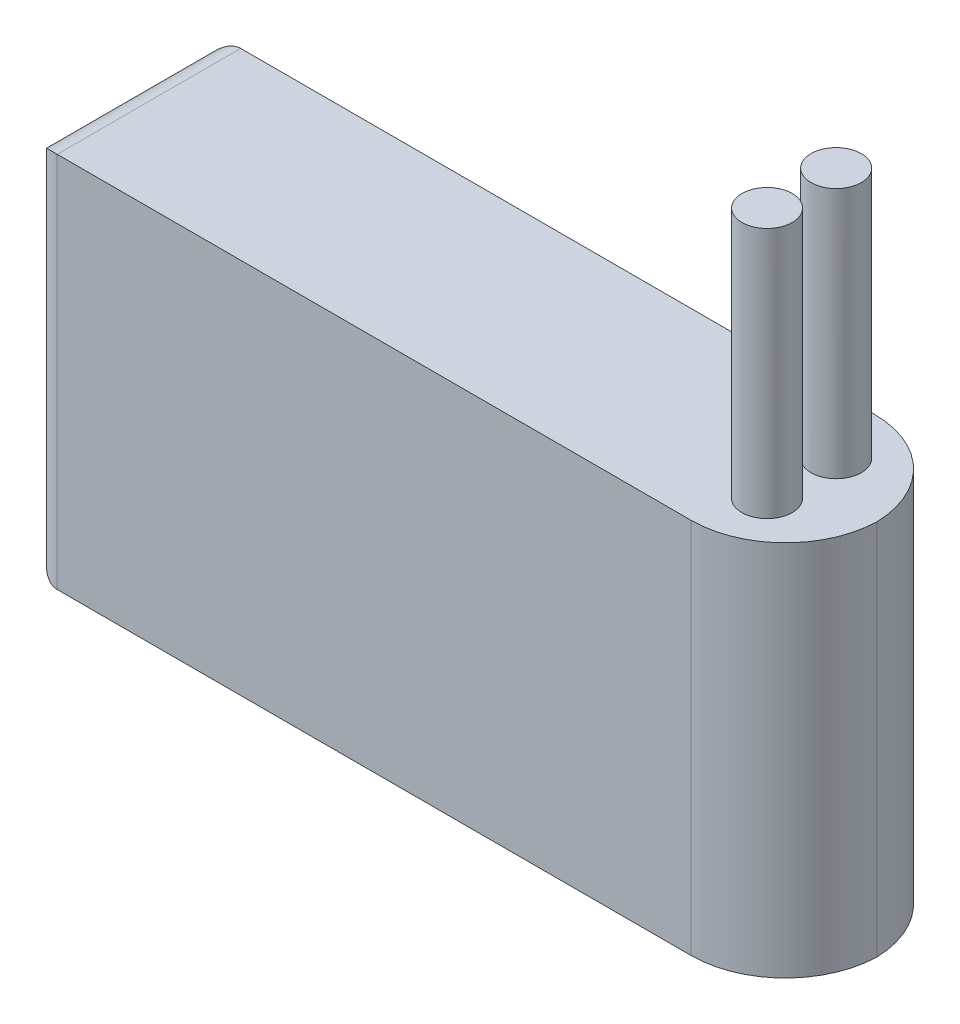
SolidWorks part; units mm, degrees
ref_plane "Front Plane" through (0, 0, 0) normal (0, 0, 1) x (1, 0, 0)
ref_plane "Top Plane" through (0, 0, 0) normal (0, 1, 0) x (1, 0, 0)
ref_plane "Right Plane" through (0, 0, 0) normal (1, 0, 0) x (0, 0, -1)
sketch "Sketch1" plane through (0, 0, 0) normal (0, 0, 1) x (1, 0, 0)
  line L1 (0, 0) -> (76.2, 0)
  line L2 (0, 0) -> (0, 38.1)
  line L3 (0, 38.1) -> (76.2, 38.1)
  line L4 (76.2, 0) -> (76.2, 38.1)
  dimension "D1" = 76.2
  dimension "D2" = 38.1
extrude "Boss-Extrude1" add sketch "Sketch1" along normal blind 18.542
fillet "Fillet1" radius 9.525 2 edges at (76.2, 19.05, 18.542) (76.2, 19.05, 0)
sketch "Sketch2" plane through (0, 38.1, 0) normal (0, 1, 0) x (1, 0, 0)
  line L0 (68.5766, -5.7785) -> (68.5766, -12.7635) construction
  line L1 (68.5766, -9.271) -> (76.1966, -9.271) construction
  circle A0 centre (68.5766, -5.7785) radius 2.54
  circle A1 centre (68.5766, -12.7635) radius 2.54
  dimension "D1" = 5.08
  dimension "D2" = 5.08
  dimension "D3" = 6.985
  dimension "D4" = 7.62
extrude "Boss-Extrude2" add sketch "Sketch2" along normal blind 25.4
fillet "Fillet2" radius 2.6035 4 edges at (0, 38.1, 9.271) (0, 19.05, 18.542) (0, 0, 9.271) (0, 19.05, 0)
